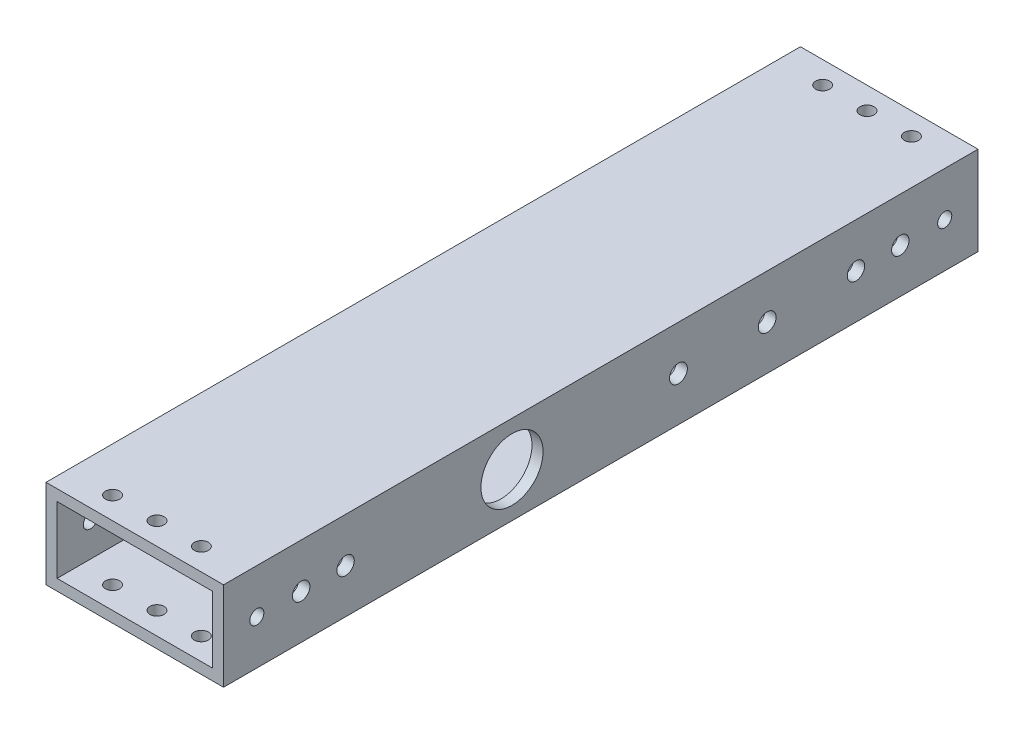
SolidWorks part; units mm, degrees
material "6061-T6 (SS)"
ref_plane "Front Plane" through (0, 0, 0) normal (0, 0, 1) x (1, 0, 0)
ref_plane "Top Plane" through (0, 0, 0) normal (0, 1, 0) x (1, 0, 0)
ref_plane "Right Plane" through (0, 0, 0) normal (1, 0, 0) x (0, 0, -1)
sketch "Sketch1" plane through (0, 0, 0) normal (0, 0, 1) x (1, 0, 0)
  line L0 (-22.225, 9.525) -> (22.225, 9.525)
  line L1 (-25.4, -12.7) -> (25.4, -12.7)
  line L2 (-25.4, -12.7) -> (-25.4, 12.7)
  line L3 (-25.4, 12.7) -> (25.4, 12.7)
  line L4 (25.4, -12.7) -> (25.4, 12.7)
  line L5 (-25.4, -12.7) -> (25.4, 12.7) construction
  line L6 (-25.4, 12.7) -> (25.4, -12.7) construction
  line L7 (22.225, -9.525) -> (22.225, 9.525)
  line L8 (-22.225, -9.525) -> (22.225, -9.525)
  line L9 (-22.225, -9.525) -> (-22.225, 9.525)
  point P0 (0, 0)
  dimension "D1" = 50.8
  dimension "D2" = 25.4
  dimension "D3" = 3.175
extrude "Boss-Extrude1" add sketch "Sketch1" along normal mid plane 215.9
sketch "Sketch2" plane through (25.4, 0, 0) normal (1, 0, 0) x (0, 0, -1)
  line L0 (-107.95, -12.7) -> (-107.95, 12.7) construction
  line L1 (0, 12.7) -> (0, -12.7) construction
  line L2 (-107.95, 12.7) -> (107.95, 12.7) construction
  line L3 (-107.95, -12.7) -> (107.95, -12.7) construction
  circle A0 centre (-98.425, 0) radius 2.0193
  circle A1 centre (98.425, 0) radius 2.0193
  circle A2 centre (-85.725, 0) radius 2.4892
  circle A3 centre (-73.025, 0) radius 2.4892
  circle A4 centre (73.025, 0) radius 2.4892
  circle A5 centre (85.725, 0) radius 2.4892
  dimension "D2" = 4.0386
  dimension "D5" = 4.9784
  dimension "D1" = 9.525
  dimension "D3" = 12.7
  dimension "D4" = 12.7
extrude "Cut-Extrude1" cut sketch "Sketch2" against normal through all
sketch "Sketch3" plane through (0, 12.7, 0) normal (0, 1, 0) x (1, 0, 0)
  line L0 (-25.4, 0) -> (25.4, 0) construction
  line L1 (-25.4, -107.95) -> (-25.4, 107.95) construction
  line L2 (25.4, -107.95) -> (25.4, 107.95) construction
  line L3 (25.4, -107.95) -> (-25.4, -107.95) construction
  circle A0 centre (-12.7, -101.6) radius 2.0193
  circle A1 centre (0, -101.6) radius 2.0193
  circle A2 centre (12.7, -101.6) radius 2.0193
  circle A3 centre (12.7, 101.6) radius 2.0193
  circle A4 centre (0, 101.6) radius 2.0193
  circle A5 centre (-12.7, 101.6) radius 2.0193
  dimension "D1" = 4.0386
  dimension "D2" = 12.7
  dimension "D3" = 12.7
  dimension "D4" = 6.35
extrude "Cut-Extrude2" cut sketch "Sketch3" against normal through all
sketch "Sketch4" plane through (25.4, 0, 0) normal (1, 0, 0) x (0, 0, -1)
  line L0 (-25.4, 0) -> (-45.1908, 0) construction
  line L1 (-16.51, 0) -> (-34.29, 0) construction
  line L8 (-25.4, 0) -> (47.625, 0) construction
  line L9 (0, 12.7) -> (0, -12.7) construction
  line L10 (-107.95, 12.7) -> (107.95, 12.7) construction
  line L11 (-107.95, -12.7) -> (107.95, -12.7) construction
  circle A0 centre (-25.4, 0) radius 8.89
  circle A9 centre (47.625, 0) radius 2.5527
  circle A10 centre (22.225, 0) radius 2.5527
  dimension "D2" = 17.78
  dimension "D3" = 25.4
  dimension "D1" = 73.025
  dimension "D4" = 5.1054
  dimension "D6" = 47.625
extrude "Cut-Extrude3" cut sketch "Sketch4" against normal through all contours A0 | A9 | A10
sketch "Sketch5" plane through (0, -12.7, 0) normal (0, -1, 0) x (1, 0, 0)
  line L0 (-25.4, 107.95) -> (-25.4, -107.95) construction
  line L1 (-25.4, 107.95) -> (25.4, 107.95) construction
  line L4 (25.4, 25.4) -> (-25.4, 25.4) construction
  line L5 (25.4, 107.95) -> (25.4, -107.95) construction
  circle A0 centre (-3.81, 69.85) radius 2.5527
  circle A1 centre (-16.51, 69.85) radius 2.5527
  circle A2 centre (-16.51, 57.15) radius 2.5527
  circle A3 centre (-3.81, 57.15) radius 2.5527
  circle A8 centre (-3.81, -6.35) radius 2.5527
  circle A9 centre (-16.51, -6.35) radius 2.5527
  circle A10 centre (-16.51, -19.05) radius 2.5527
  circle A11 centre (-3.81, -19.05) radius 2.5527
  dimension "D3" = 5.1054
  dimension "D4" = 8.89
  dimension "D7" = 12.7
  dimension "D12" = 82.55
  dimension "D5" = 31.75
  dimension "D6" = 12.7
  dimension "D1" = 2
  dimension "D2" = 2
extrude "Cut-Extrude4" cut sketch "Sketch5" against normal up to next
